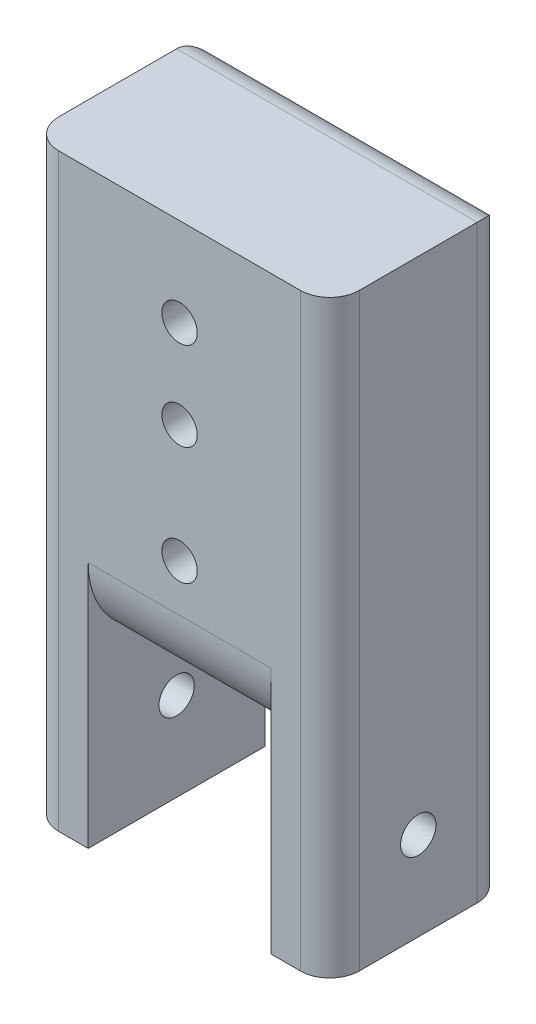
SolidWorks part; units mm, degrees
ref_plane "Front Plane" through (0, 0, 0) normal (0, 0, 1) x (1, 0, 0)
ref_plane "Top Plane" through (0, 0, 0) normal (0, 1, 0) x (1, 0, 0)
ref_plane "Right Plane" through (0, 0, 0) normal (1, 0, 0) x (0, 0, -1)
sketch "Sketch1" plane through (0, 0, 0) normal (0, 0, 1) x (1, 0, 0)
  line L0 (0, 0) -> (51, 0)
  line L1 (51, 0) -> (51, -100)
  line L2 (0, 0) -> (0, -100)
  line L3 (0, -100) -> (10, -100)
  line L4 (51, -100) -> (41, -100)
  line L5 (41, -100) -> (41, -73)
  line L6 (41, -73) -> (10, -73)
  line L7 (10, -73) -> (10, -100)
extrude "Boss-Extrude1" add sketch "Sketch1" along normal blind 30
sketch "Sketch2" plane through (51, 0, 0) normal (1, 0, 0) x (0, 0, -1)
  circle A0 centre (-15, -85) radius 3
extrude "Cut-Extrude1" cut sketch "Sketch2" against normal blind 111
sketch "Sketch3" plane through (0, 0, 0) normal (0, 0, -1) x (-1, 0, 0)
  circle A5 centre (-25.5, -15) radius 3
  circle A6 centre (-25.5, -30) radius 3
  circle A7 centre (-25.5, -50) radius 3
extrude "Cut-Extrude2" cut sketch "Sketch3" against normal blind 111
fillet "Fillet1" radius 5 3 edges at (25.5, 0, 0) (0, -50, 0) (51, -50, 0)
fillet "Fillet2" radius 5 2 edges at (0, -50, 30) (51, -50, 30)
fillet "Fillet3" radius 15 2 edges at (25.5, -73, 30) (25.5, -73, 0)
